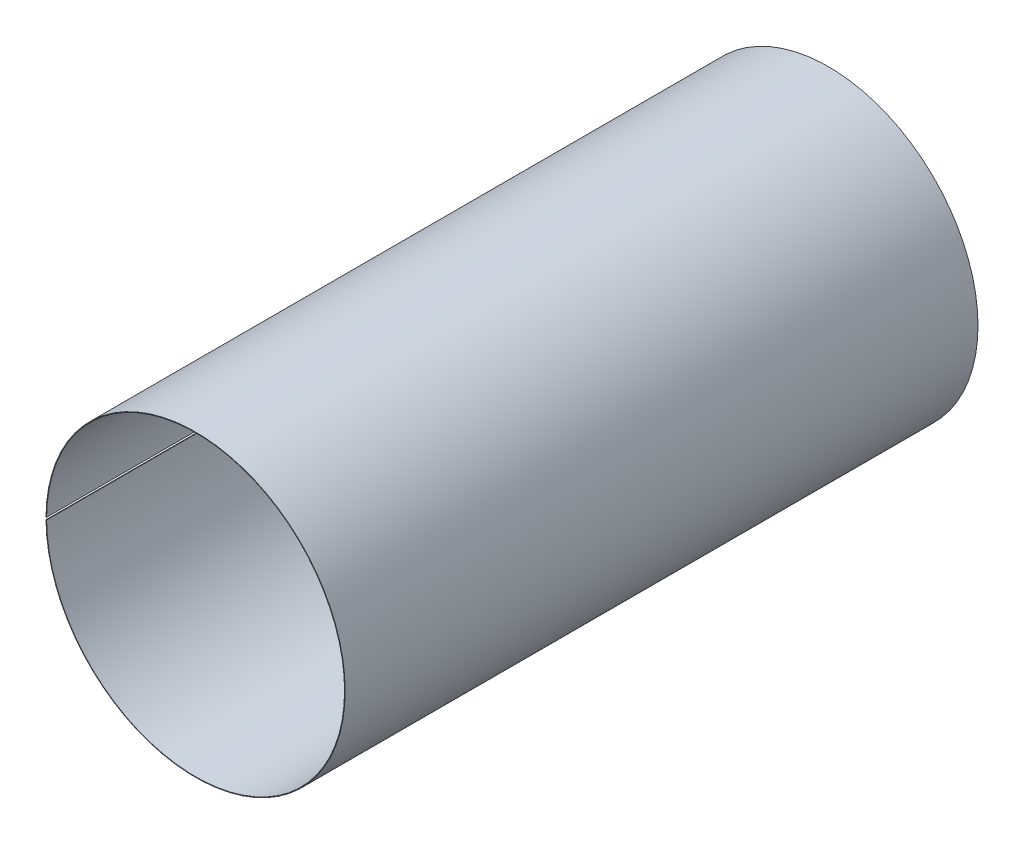
SolidWorks part; units mm, degrees
ref_plane "Front" through (0, 0, 0) normal (0, 0, 1) x (1, 0, 0)
ref_plane "Top" through (0, 0, 0) normal (0, 1, 0) x (1, 0, 0)
ref_plane "Right" through (0, 0, 0) normal (1, 0, 0) x (0, 0, -1)
sketch "Sketch2" plane through (0, 0, 0) normal (0, 0, 1) x (1, 0, 0)
  circle A0 centre (0, 0) radius 66.04
  circle A1 centre (0, 0) radius 65.786
  dimension "D1" = 132.08
  dimension "D2" = 131.572
extrude "Boss-Extrude1" add sketch "Sketch2" along normal blind 279.4
sketch "Sketch3" plane through (0, 0, 279.4) normal (0, 0, 1) x (1, 0, 0)
  line L0 (-71.4518, 0) -> (70.1682, 0) construction
  line L1 (0, 68.3498) -> (0, -67.2802) construction
ref_plane "Plane1" through (-66.04, 0, 0) normal (-1, 0, 0) x (0, 0, 1)
sketch "Sketch5" plane through (-66.04, 0, 0) normal (-1, 0, 0) x (0, 0, 1)
  line L0 (-8.3863, 0) -> (289.133, 0) construction
  line L1 (0, 0.508) -> (279.4, 0.508)
  line L2 (0, 66.04) -> (0, -66.04) construction
  line L3 (279.4, 68.3498) -> (279.4, -67.2802) construction
  line L4 (279.4, 0.508) -> (279.4, -0.508)
  line L5 (0, 0.508) -> (0, -0.508)
  line L6 (0, -0.508) -> (279.4, -0.508)
  point P12 (279.4, 0)
  point P13 (0, 0)
  dimension "D1" = 0.508
extrude "Cut-Extrude1" cut sketch "Sketch5" against normal blind 10.16 and the other way through all
